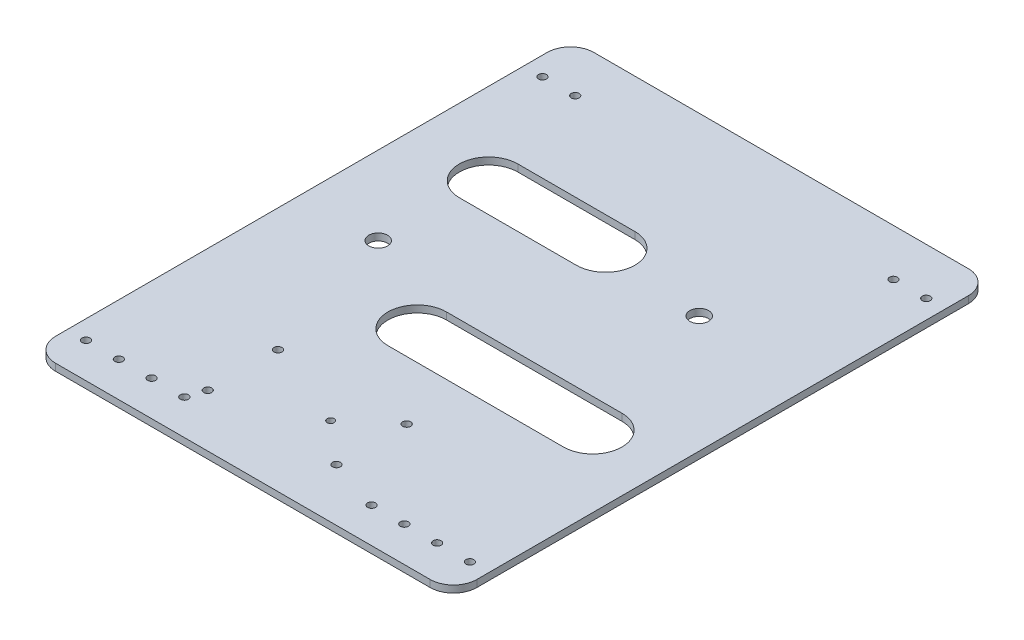
SolidWorks part; units mm, degrees
ref_plane "Front Plane" through (0, 0, 0) normal (0, 0, 1) x (1, 0, 0)
ref_plane "Top Plane" through (0, 0, 0) normal (0, 1, 0) x (1, 0, 0)
ref_plane "Right Plane" through (0, 0, 0) normal (1, 0, 0) x (0, 0, -1)
sketch "Sketch1" plane through (0, 0, 0) normal (0, 1, 0) x (1, 0, 0)
  line L1 (-90, 140) -> (90, 140)
  line L2 (-90, 140) -> (-90, -90)
  line L3 (-90, -90) -> (90, -90)
  line L4 (90, 140) -> (90, -90)
  line L5 (-90, 140) -> (90, -90) construction
  line L6 (-90, -90) -> (90, 140) construction
  point P0 (0, 25)
  point P6 (0, 0)
  point P7 (0, 0)
  dimension "D1" = 230
  dimension "D2" = 180
  dimension "D3" = 25
extrude "Boss-Extrude1" add sketch "Sketch1" along normal blind 3
fillet "Fillet1" radius 10 4 edges at (-90, 1.5, -140) (-90, 1.5, 90) (90, 1.5, -140) (90, 1.5, 90)
sketch "Sketch2" plane through (0, 3, 0) normal (0, 1, 0) x (1, 0, 0)
  circle A0 centre (-82, 120) radius 1.7
  circle A1 centre (-68, 120) radius 1.7
  circle A2 centre (68, 120) radius 1.7
  circle A3 centre (82, 120) radius 1.7
  circle A4 centre (-82, -75) radius 1.7
  circle A5 centre (-68, -75) radius 1.7
  circle A6 centre (68, -75) radius 1.7
  circle A7 centre (82, -75) radius 1.7
  circle A32 centre (-54, -75) radius 1.7
  circle A33 centre (54, -75) radius 1.7
  circle A34 centre (-40, -75) radius 1.7
  circle A35 centre (40, -75) radius 1.7
  dimension "D1" = 3.4
  dimension "D11" = 14
  dimension "D18" = 14
  dimension "D19" = 14
  dimension "D20" = 14
  dimension "D2" = 14
  dimension "D3" = 14
  dimension "D4" = 82
  dimension "D5" = 82
  dimension "D6" = 120
  dimension "D7" = 75
extrude "Cut-Extrude1" cut sketch "Sketch2" against normal up to surface (3 mm away) up to face at (0, 0, -25)
sketch "Sketch3" plane through (0, 3, 0) normal (0, 1, 0) x (1, 0, 0)
  circle A0 centre (40, 65) radius 4
  circle A1 centre (-56.482, 24.3143) radius 4
extrude "Cut-Extrude2" cut sketch "Sketch3" against normal through all
sketch "Sketch4" plane through (0, 3, 0) normal (0, 1, 0) x (1, 0, 0)
  circle A0 centre (0, -52.5) radius 1.5
  circle A1 centre (17.5, -37.5) radius 1.7
  circle A2 centre (17.5, -67.5) radius 1.7
  circle A3 centre (-37.5, -37.5) radius 1.7
  circle A4 centre (-37.5, -67.5) radius 1.7
  dimension "D1" = 55
  dimension "D2" = 30
  dimension "D5" = 3.4
  dimension "D3" = 15
  dimension "D4" = 17.5
extrude "Cut-Extrude3" cut sketch "Sketch4" against normal through all
sketch "Sketch6" plane through (0, 3, 0) normal (0, 1, 0) x (1, 0, 0)
  line L0 (-55, 70) -> (-5, 70) construction
  line L1 (-55, 82.5) -> (-5, 82.5)
  line L2 (-55, 57.5) -> (-5, 57.5)
  line L3 (-15.5, 0) -> (59.5, 0) construction
  line L4 (-15.5, 12.5) -> (59.5, 12.5)
  line L5 (-15.5, -12.5) -> (59.5, -12.5)
  arc A0 (-55, 82.5) -> (-55, 57.5) centre (-55, 70) ccw
  arc A1 (-5, 57.5) -> (-5, 82.5) centre (-5, 70) ccw
  arc A2 (-15.5, 12.5) -> (-15.5, -12.5) centre (-15.5, 0) ccw
  arc A3 (59.5, -12.5) -> (59.5, 12.5) centre (59.5, 0) ccw
  point P2 (-30, 70)
  point P7 (22, 0)
  dimension "D1" = 25
  dimension "D2" = 25
  dimension "D3" = 50
  dimension "D4" = 75
  dimension "D5" = 30
  dimension "D6" = 22
  dimension "D7" = 70
extrude "Cut-Extrude4" cut sketch "Sketch6" against normal through all
